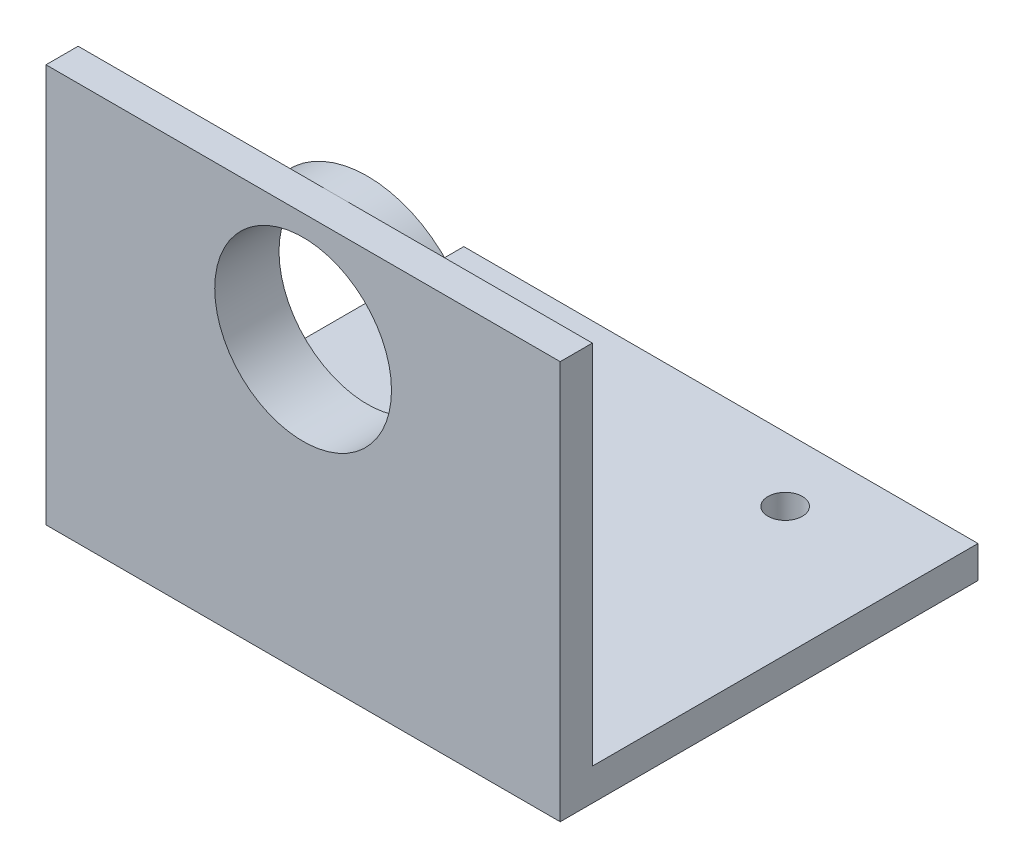
SolidWorks part; units mm, degrees
material "6061 Alloy"
ref_plane "Front Plane" through (0, 0, 0) normal (0, 0, 1) x (1, 0, 0)
ref_plane "Top Plane" through (0, 0, 0) normal (0, 1, 0) x (1, 0, 0)
ref_plane "Right Plane" through (0, 0, 0) normal (1, 0, 0) x (0, 0, -1)
sketch "Sketch2" plane through (0, 0, 0) normal (0, 1, 0) x (1, 0, 0)
  line L1 (-25.4, -12.7) -> (25.4, -12.7)
  line L2 (-25.4, -12.7) -> (-25.4, 12.7)
  line L4 (25.4, -12.7) -> (25.4, 12.7)
  line L5 (-25.4, -12.7) -> (25.4, 12.7) construction
  line L6 (-25.4, 12.7) -> (25.4, -12.7) construction
  line L8 (-25.4, 12.7) -> (-25.4, 25.4)
  line L9 (-25.4, 25.4) -> (25.4, 25.4)
  line L10 (25.4, 12.7) -> (25.4, 25.4)
  line L11 (0, 0) -> (0, 25.4) construction
  line L12 (-12.7, 19.05) -> (12.7, 19.05) construction
  point P0 (0, 0)
  point P6 (0, 19.05)
  point P14 (-12.7, 19.05)
  point P15 (12.7, 19.05)
  dimension "D1" = 50.8
  dimension "D2" = 25.4
  dimension "D3" = 12.7
  dimension "D4" = 25.4
  dimension "D5" = 6.35
extrude "Boss-Extrude1" add sketch "Sketch2" along normal blind 3.175
sketch "Sketch3" plane through (0, 3.175, 0) normal (0, 1, 0) x (1, 0, 0)
  line L0 (-25.4, -12.7) -> (25.4, -12.7) construction
  line L1 (-22.225, -9.525) -> (22.225, -9.525)
  line L2 (-22.225, -9.525) -> (-22.225, 9.525)
  line L3 (-22.225, 9.525) -> (22.225, 9.525)
  line L4 (22.225, -9.525) -> (22.225, 9.525)
  line L5 (-22.225, -9.525) -> (22.225, 9.525) construction
  line L6 (-22.225, 9.525) -> (22.225, -9.525) construction
  line L7 (-25.4, 25.4) -> (-25.4, -12.7) construction
  point P0 (0, 0)
  dimension "D2" = 3.175
  dimension "D1" = 3.175
extrude "Boss-Extrude2" [suppressed] add sketch "Sketch3" along normal blind 3.175
hole_wizard "M3 Clearance Hole1" positions "3DSketch1" profile "Sketch6" hole size "M3" standard "ANSI Metric" end condition through all
sketch3d "3DSketch1"
  point P0 (-12.7, 0, -19.05)
  point P3 (12.7, 0, -19.05)
sketch "Sketch6" plane through (-12.7, 0, -19.05) normal (1, 0, 0) x (0, 0, -1)
  line L0 (0, 0) -> (0, 3.175)
  line L1 (0, 3.175) -> (1.7, 3.175)
  line L2 (1.7, 3.175) -> (1.7, 0)
  line L5 (1.7, 0) -> (0, 0)
  line L11 (0, -6.35) -> (0, 107.95) construction
  dimension "Thru Hole Dia." = 3.4
  dimension "Thru Hole Depth" = 3.175
sketch "Sketch7" plane through (0, 0, 0) normal (0, -1, 0) x (1, 0, 0)
  line L0 (25.4, 12.7) -> (25.4, -25.4) construction
  line L1 (-25.4, 12.7) -> (25.4, 12.7)
  line L2 (-25.4, 12.7) -> (-25.4, 15.875)
  line L3 (-25.4, 15.875) -> (25.4, 15.875)
  line L4 (25.4, 12.7) -> (25.4, 15.875)
  dimension "D1" = 3.175
extrude "Boss-Extrude3" add sketch "Sketch7" against normal blind 39.37
sketch "Sketch8" plane through (0, 0, 12.7) normal (0, 0, -1) x (-1, 0, 0)
  line L0 (-10.795, 28.575) -> (-10.795, 3.175)
  line L2 (-10.795, 3.175) -> (10.795, 3.175)
  line L4 (10.795, 3.175) -> (10.795, 28.575)
  line L5 (25.4, 3.175) -> (-25.4, 3.175) construction
  arc A0 (10.795, 28.575) -> (-10.795, 28.575) centre (0, 28.575) ccw
  dimension "D2" = 21.59
  dimension "D1" = 25.4
extrude "Boss-Extrude4" add sketch "Sketch8" along normal blind 3.175
sketch "Sketch9" plane through (0, 0, 9.525) normal (0, 0, -1) x (-1, 0, 0)
  circle A0 centre (0, 28.575) radius 8.7312
  dimension "D1" = 17.4625
extrude "Cut-Extrude1" cut sketch "Sketch9" against normal through all
fillet "Fillet1" radius 3.175 2 edges at (-10.795, 3.175, 11.1125) (10.795, 3.175, 11.1125)
equation "\"D2@Sketch3\"=\"D1@Sketch3\""
